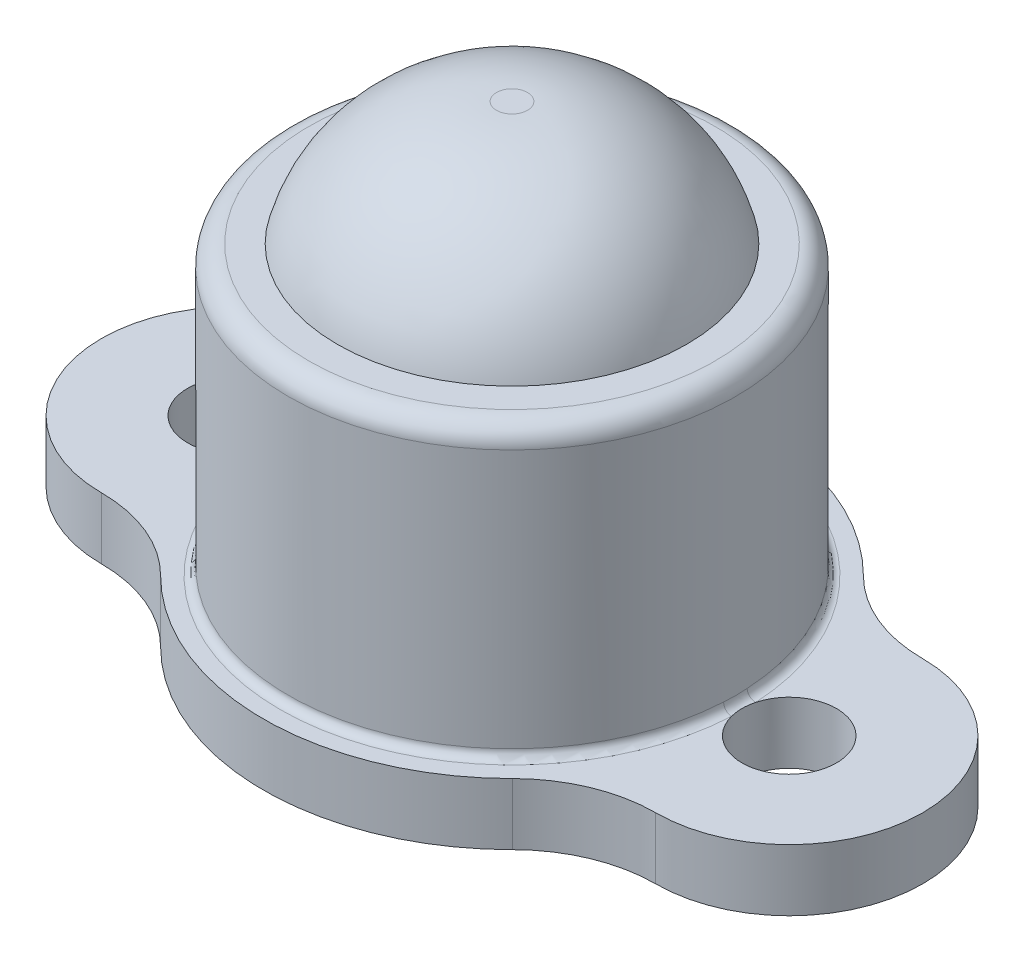
SolidWorks part; units mm, degrees
ref_plane "Front Plane" through (0, 0, 0) normal (0, 0, 1) x (1, 0, 0)
ref_plane "Top Plane" through (0, 0, 0) normal (0, 1, 0) x (1, 0, 0)
ref_plane "Right Plane" through (0, 0, 0) normal (1, 0, 0) x (0, 0, -1)
sketch "Sketch1" plane through (0, 0, 0) normal (0, 1, 0) x (1, 0, 0)
  line L0 (0, 0) -> (0, 6.05) construction
  line L1 (0, 0) -> (-3.5, 0) construction
  arc A0 (-4.2824, -4.2736) -> (4.2824, -4.2736) centre (0, 0) ccw
  circle A1 centre (0, 0) radius 2.9469
  arc A2 (-6.75, 3.25) -> (-6.75, -3.25) centre (-6.75, 0) ccw
  arc A3 (6.75, 3.25) -> (6.75, -3.25) centre (6.75, 0) cw
  arc A4 (-6.75, 3.25) -> (-4.2824, 4.2736) centre (-6.75, 6.7362) ccw
  arc A5 (-6.75, -3.25) -> (-4.2824, -4.2736) centre (-6.75, -6.7362) cw
  arc A6 (6.75, -3.25) -> (4.2824, -4.2736) centre (6.75, -6.7362) ccw
  arc A7 (6.75, 3.25) -> (4.2824, 4.2736) centre (6.75, 6.7362) cw
  arc A8 (4.2824, 4.2736) -> (-4.2824, 4.2736) centre (0, 0) ccw
  dimension "D1" = 12.1
  dimension "D2" = 5.8938
  dimension "D3" = 6.5
  dimension "D4" = 6.75
extrude "Boss-Extrude1" add sketch "Sketch1" along normal blind 1.5 contours A2 A0 | A0 A1 | A3 A0 region at (-5.3247, 0, 3.3001)
sketch "Sketch2" plane through (0, 1.5, 0) normal (0, 1, 0) x (1, 0, 0)
  line L0 (0, 0) -> (0, -6.05) construction
  circle A0 centre (-6.75, 0) radius 1.15
  arc A2 (-6.75, 3.25) -> (-6.75, -3.25) centre (-6.75, 0) ccw construction
  arc A3 (-4.2824, -4.2736) -> (4.2824, -4.2736) centre (0, 0) ccw construction
  circle A4 centre (6.75, 0) radius 1.15
  dimension "D1" = 2.3
extrude "Cut-Extrude1" cut sketch "Sketch2" against normal through all
sketch "Sketch3" plane through (0, 1.5, 0) normal (0, 1, 0) x (1, 0, 0)
  circle A2 centre (0, 0) radius 5.4469
  circle A3 centre (0, 0) radius 5.4469
  arc A4 (-6.75, 3.25) -> (-6.75, -3.25) centre (-6.75, 0) ccw
  arc A5 (-4.2824, -4.2736) -> (4.2824, -4.2736) centre (0, 0) ccw
  arc A6 (6.75, -3.25) -> (6.75, 3.25) centre (6.75, 0) ccw
  arc A7 (4.2824, 4.2736) -> (6.75, 3.25) centre (6.75, 6.7362) ccw
  arc A8 (-6.75, 3.25) -> (-6.75, -3.25) centre (-6.75, 0) ccw
  arc A9 (-4.2824, -4.2736) -> (4.2824, -4.2736) centre (0, 0) ccw
  arc A10 (6.75, -3.25) -> (6.75, 3.25) centre (6.75, 0) ccw
  arc A11 (4.2824, 4.2736) -> (6.75, 3.25) centre (6.75, 6.7362) ccw
  arc A18 (4.2824, 4.2736) -> (-4.2824, 4.2736) centre (0, 0) ccw
  arc A19 (4.2824, 4.2736) -> (-4.2824, 4.2736) centre (0, 0) ccw
  arc A20 (-6.75, 3.25) -> (-4.2824, 4.2736) centre (-6.75, 6.7362) ccw
  arc A21 (-6.75, 3.25) -> (-4.2824, 4.2736) centre (-6.75, 6.7362) ccw
  arc A22 (-4.2824, -4.2736) -> (-6.75, -3.25) centre (-6.75, -6.7362) ccw
  arc A23 (-4.2824, -4.2736) -> (-6.75, -3.25) centre (-6.75, -6.7362) ccw
  arc A24 (6.75, -3.25) -> (4.2824, -4.2736) centre (6.75, -6.7362) ccw
  arc A25 (6.75, -3.25) -> (4.2824, -4.2736) centre (6.75, -6.7362) ccw
  circle M20 centre (0, 0) radius 2.9469
  dimension "D1" = 0
  dimension "D2" = 2.5
extrude "Boss-Extrude2" add sketch "Sketch3" along normal blind 7 contours A3 M20 region at (-5.2928, 1.5, 0)
sketch "Sketch4" plane through (0, 8.5, 0) normal (0, 1, 0) x (1, 0, 0)
  circle A0 centre (0, 0) radius 4.25
  dimension "D1" = 8.5
extrude "Boss-Extrude3" add sketch "Sketch4" along normal blind 3
fillet "Fillet1" radius 4 1 edges at (0, 11.5, 4.25)
fillet "Fillet2" radius 0.5 1 edges at (0, 8.5, 5.4469)
fillet "Fillet3" radius 0.2 1 edges at (0, 1.5, 5.4469)
